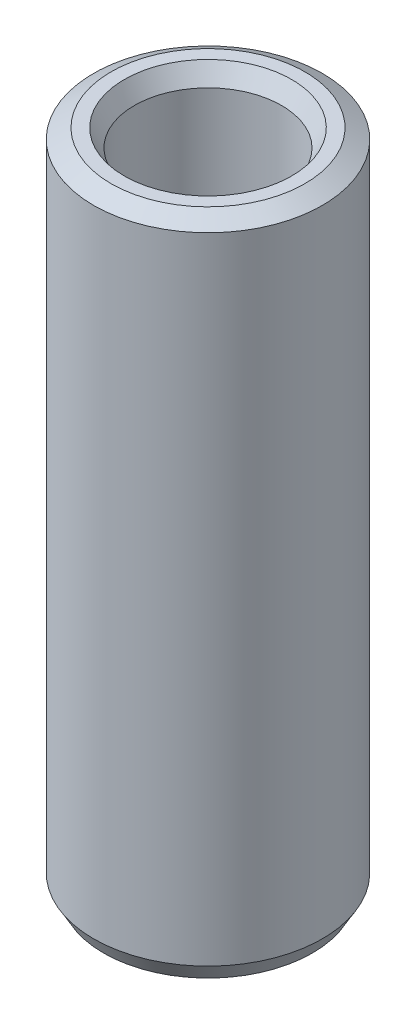
SolidWorks part; units mm, degrees
ref_plane "Front Plane" through (0, 0, 0) normal (0, 0, 1) x (1, 0, 0)
ref_plane "Top Plane" through (0, 0, 0) normal (0, 1, 0) x (1, 0, 0)
ref_plane "Right Plane" through (0, 0, 0) normal (1, 0, 0) x (0, 0, -1)
sketch "Sketch1" plane through (0, 0, 0) normal (0, 1, 0) x (1, 0, 0)
  circle A0 centre (0, 0) radius 45
  dimension "SLEEVE_OD" = 90
extrude "Boss-Extrude1" add sketch "Sketch1" along normal blind 260.6933
sketch "Sketch2" plane through (0, 0, 0) normal (0, 1, 0) x (1, 0, 0)
  circle A0 centre (0, 0) radius 28.9462
  dimension "BORE_D" = 57.8923
extrude "Cut-Extrude1" cut sketch "Sketch2" along normal through all
chamfer "Chamfer1" distance 3.9674 angle 60 4 edges at (0, 260.6933, 28.9462) (0, 0, 28.9462) (0, 0, 45) (0, 260.6933, 45) first distance on face at (0, 260.6933, 28.9462) first distance on face at (0, 0, 28.9462) first distance on face at (0, 260.6933, 45)
